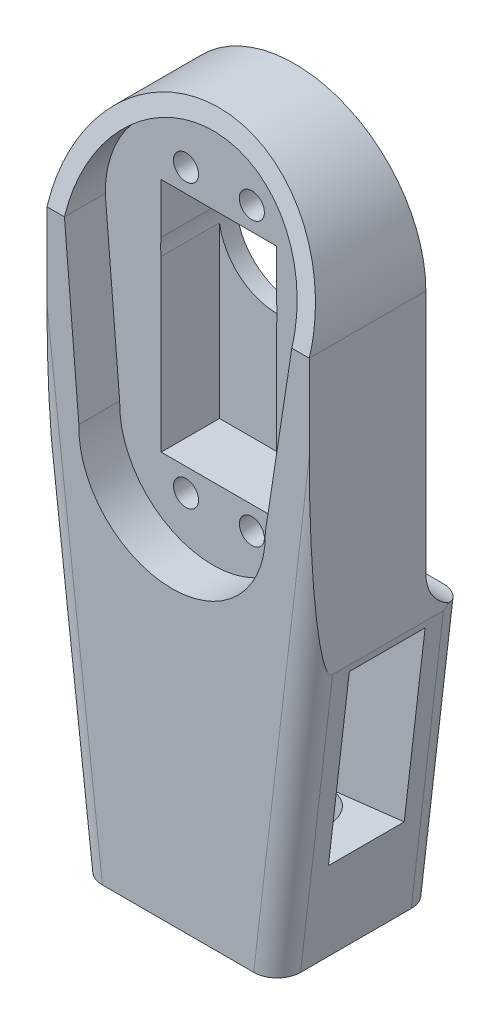
SolidWorks part; units mm, degrees
ref_plane "Front Plane" through (0, 0, 0) normal (0, 0, 1) x (1, 0, 0)
ref_plane "Top Plane" through (0, 0, 0) normal (0, 1, 0) x (1, 0, 0)
ref_plane "Right Plane" through (0, 0, 0) normal (1, 0, 0) x (0, 0, -1)
sketch "Sketch1" plane through (0, 0, 0) normal (0, 0, 1) x (1, 0, 0)
  line L0 (-19, 19) -> (19, 19) construction
  line L1 (22.5, 0) -> (22.5, -49)
  line L2 (22.5, -49) -> (-22.5, -49)
  line L3 (-22.5, -49) -> (-22.5, 0)
  line L4 (0, 17) -> (0, 0) construction
  line L5 (-25.223, -18.3377) -> (32.3676, -18.3377) construction
  arc A0 (22.5, 0) -> (-22.5, 0) centre (0, 0) ccw
  point P6 (-2.6072, 22.3484)
  dimension "D3" = 45
extrude "Boss-Extrude1" add sketch "Sketch1" along normal mid plane 20
sketch "Sketch2" plane through (0, 0, 10) normal (0, 0, 1) x (1, 0, 0)
  line L1 (-22.5, -49) -> (22.5, -49) construction
  line L6 (-19.5, 0) -> (-19.5, -46)
  line L7 (-19.5, -46) -> (19.5, -46)
  line L8 (19.5, -46) -> (19.5, 0)
  line L9 (-19.5, 0) -> (-17.0296, -29.5981)
  line L11 (14.9603, -29.5966) -> (19.5, 0)
  arc A1 (-17.0296, -29.5981) -> (14.9603, -29.5966) centre (-1.0346, -30) ccw
  arc A2 (19.5, 0) -> (-19.5, 0) centre (0, 0) ccw
  arc A3 (19.5, 0) -> (-19.5, 0) centre (0, 0) ccw
  point P1 (-1.0339, -46)
  dimension "D2" = 16
  dimension "D3" = 3
  dimension "D1" = 3
extrude "Cut-Extrude1" cut sketch "Sketch2" against normal blind 7
ref_plane "Plane1" through (0, 0, 0) normal (-1, 0, 0) x (0, 0, 1)
sketch "Sketch4" plane through (0, 0, 0) normal (-1, 0, 0) x (0, 0, 1)
  line L0 (10, 0) -> (10, 22.5)
  line L2 (10, 22.5) -> (3, 22.5)
  line L3 (3, 22.5) -> (10, 0)
  dimension "D1" = 7
  dimension "D2" = 22.5
extrude "Cut-Extrude3" cut sketch "Sketch4" against normal through all both and the other way through all
sketch "Sketch5" plane through (0, 0, 10) normal (0, 0, 1) x (1, 0, 0)
  line L0 (0, -49) -> (0, -96) construction
  line L1 (-22.5, -49) -> (22.5, -49) construction
  line L2 (0, 11) -> (0, -11) construction
  line L3 (-17, -96) -> (17, -96)
  line L4 (-22.5, -49) -> (-17, -96)
  line L5 (-22.5, -49) -> (22.5, -49)
  line L6 (22.5, -49) -> (17, -96)
  point P10 (0, -96)
  dimension "D1" = 47
  dimension "D2" = 34
extrude "Boss-Extrude2" add sketch "Sketch5" against normal blind 27
sketch "Sketch6" plane through (-27.8526, -3.2594, 0) normal (-0.9932, -0.1162, 0) x (0, 0, 1)
  line L0 (-17, -93.3735) -> (10, -93.3735) construction
  line L1 (-10, -52.3735) -> (3, -52.3735)
  line L2 (-10, -52.3735) -> (-10, -82.3735)
  line L3 (-10, -82.3735) -> (3, -82.3735)
  line L4 (3, -52.3735) -> (3, -82.3735)
  line L5 (10, -46.0528) -> (10, -93.3735) construction
  line L6 (-17, -46.0528) -> (-17, -93.3735) construction
  dimension "D1" = 11
  dimension "D2" = 30
  dimension "D3" = 7
  dimension "D4" = 7
extrude "Cut-Extrude4" cut sketch "Sketch6" against normal through all
fillet "Fillet1" radius 7 1 edges at (0, -49, -10)
fillet "Fillet2" radius 4 4 edges at (19.75, -72.5, -17) (-19.75, -72.5, -17) (-19.75, -72.5, 10) (19.75, -72.5, 10)
sketch "Sketch8" plane through (0, -96, 0) normal (0, -1, 0) x (1, 0, 0)
  line L0 (12, 10) -> (12, -17) construction
  line L1 (-12.9727, 10) -> (12.9727, 10) construction
  line L2 (-12.9727, -17) -> (12.9727, -17) construction
  line L3 (17, -13) -> (17, 6) construction
  line L4 (12, -3.5) -> (0, -3.5) construction
  line L5 (0, 11) -> (0, -11) construction
  circle A0 centre (5.5, -3.5) radius 6.5
  dimension "D2" = 13
  dimension "D1" = 5
extrude "Cut-Extrude5" cut sketch "Sketch8" against normal blind 27
sketch "Sketch9" plane through (9.5741, -81.8152, 0) normal (-0.1162, 0.9932, 0) x (0.9932, 0.1162, 0)
  line L0 (-28.0427, 10) -> (-28.0427, -3) construction
  line L1 (-25.0427, -3) -> (6.2748, -3)
  line L2 (-28.0427, -3) -> (-28.0427, 10) construction
  line L3 (-25.0427, 10) -> (6.2748, 10)
  line L4 (9.2748, -3) -> (9.2748, 10) construction
  line L5 (9.2748, -3) -> (9.2748, 10) construction
  line L6 (6.2748, 10) -> (6.2748, -3)
  line L7 (-25.0427, 10) -> (-25.0427, -3)
  line L8 (-24.0427, 17) -> (1.7269, 17) construction
  ellipse E0 centre (-4.1019, 3.5) end of major axis (-10.6463, 3.5) minor radius 6.5 (-4.1019, -3) -> (-4.1019, 10) ccw construction
  ellipse E1 centre (-4.1019, 3.5) end of major axis (-10.6463, 3.5) minor radius 6.5 (-4.1019, -3) -> (-4.1019, 10) ccw
  point P19 (9.2748, 3.5)
  dimension "D1" = 13
  dimension "D2" = 3
  dimension "D3" = 3
  dimension "D4" = 7
sketch "Sketch11" plane through (0, 0, 3) normal (0, 0, 1) x (1, 0, 0)
  line L0 (-9.9, -13.3955) -> (9.9, -13.3955) construction
  line L1 (-9.9, 6.8545) -> (9.9, 6.8545)
  line L2 (-9.9, 6.8545) -> (-9.9, -33.6455)
  line L3 (-9.9, -33.6455) -> (9.9, -33.6455)
  line L4 (9.9, 6.8545) -> (9.9, -33.6455)
  line L5 (0, 6.8545) -> (0, -33.6455) construction
  circle A0 centre (5.65, 10.8045) radius 2.15
  circle A1 centre (-5.65, 10.8045) radius 2.15
  circle A2 centre (5.65, -37.5955) radius 2.15
  circle A3 centre (-5.65, -37.5955) radius 2.15
  point P11 (0, -13.3955)
  dimension "D3" = 4.3
  dimension "D1" = 19.8
  dimension "D2" = 40.5
  dimension "D4" = 48.4
  dimension "D5" = 11.3
extrude "Cut-Extrude7" cut sketch "Sketch11" against normal blind 10
sketch "Sketch12" plane through (0, 0, -7) normal (0, 0, 1) x (1, 0, 0)
  line L0 (0, 6.8545) -> (0, -33.6455) construction
  line L2 (-9.9, 6.8545) -> (9.9, 6.8545) construction
  circle A0 centre (0, -3.1455) radius 10
  dimension "D1" = 20
  dimension "D2" = 10
extrude "Cut-Extrude8" cut sketch "Sketch12" against normal through all both and the other way through all
ref_point "Point1"
ref_point "Point2"
